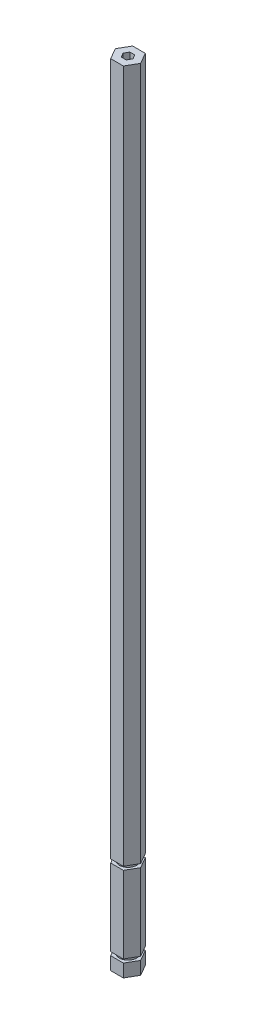
SolidWorks part; units mm, degrees
ref_plane "Front Plane" through (0, 0, 0) normal (0, 0, 1) x (1, 0, 0)
ref_plane "Top Plane" through (0, 0, 0) normal (0, 1, 0) x (1, 0, 0)
ref_plane "Right Plane" through (0, 0, 0) normal (1, 0, 0) x (0, 0, -1)
sketch "Sketch1" plane through (0, 0, 0) normal (0, 1, 0) x (1, 0, 0)
  line L9 (7.3323, 0) -> (3.6662, 6.35)
  line L10 (3.6662, 6.35) -> (-3.6662, 6.35)
  line L11 (-3.6662, 6.35) -> (-7.3323, 0)
  line L12 (-7.3323, 0) -> (-3.6662, -6.35)
  line L13 (-3.6662, -6.35) -> (3.6662, -6.35)
  line L14 (3.6662, -6.35) -> (7.3323, 0)
  line L15 (1.4434, 2.5) -> (-1.4434, 2.5)
  line L16 (-1.4434, 2.5) -> (-2.8868, 0)
  line L17 (-2.8868, 0) -> (-1.4434, -2.5)
  line L18 (-1.4434, -2.5) -> (1.4434, -2.5)
  line L19 (1.4434, -2.5) -> (2.8868, 0)
  line L20 (2.8868, 0) -> (1.4434, 2.5)
  circle A0 centre (0, 0) radius 6.35 construction
  circle A1 centre (0, 0) radius 2.5 construction
  dimension "D1" = 12.7
  dimension "D2" = 5
extrude "Boss-Extrude1" add sketch "Sketch1" along normal blind 457.2
sketch "Sketch3" plane through (0, 0, 0) normal (1, 0, 0) x (0, 0, -1)
  line L0 (0, 457.2) -> (0, 431.8613) construction
  line L2 (0, 457.2) -> (0, 0) construction
  line L7 (-5.0165, 56.007) -> (5.0165, 56.007) construction
  line L10 (5.0165, 56.007) -> (7.5565, 56.007)
  line L11 (5.0165, 56.007) -> (5.0165, 53.975)
  line L12 (5.0165, 53.975) -> (7.5565, 53.975)
  line L13 (7.5565, 56.007) -> (7.5565, 53.975)
  line L14 (0, 0) -> (6.35, 0) construction
  line L15 (5.0165, 53.975) -> (5.0165, 9.525) construction
  line L16 (5.0165, 31.75) -> (-13.2923, 31.75) construction
  line L17 (5.0165, 7.493) -> (7.5565, 7.493)
  line L18 (5.0165, 7.493) -> (5.0165, 9.525)
  line L19 (5.0165, 9.525) -> (7.5565, 9.525)
  line L20 (7.5565, 7.493) -> (7.5565, 9.525)
  point P7 (0, 56.007)
  dimension "D1" = 10.033
  dimension "D2" = 53.975
  dimension "D3" = 2.032
  dimension "D4" = 2.54
  dimension "D5" = 44.45
revolve "Cut-Revolve2" cut sketch "Sketch3" angle 360 about L0
